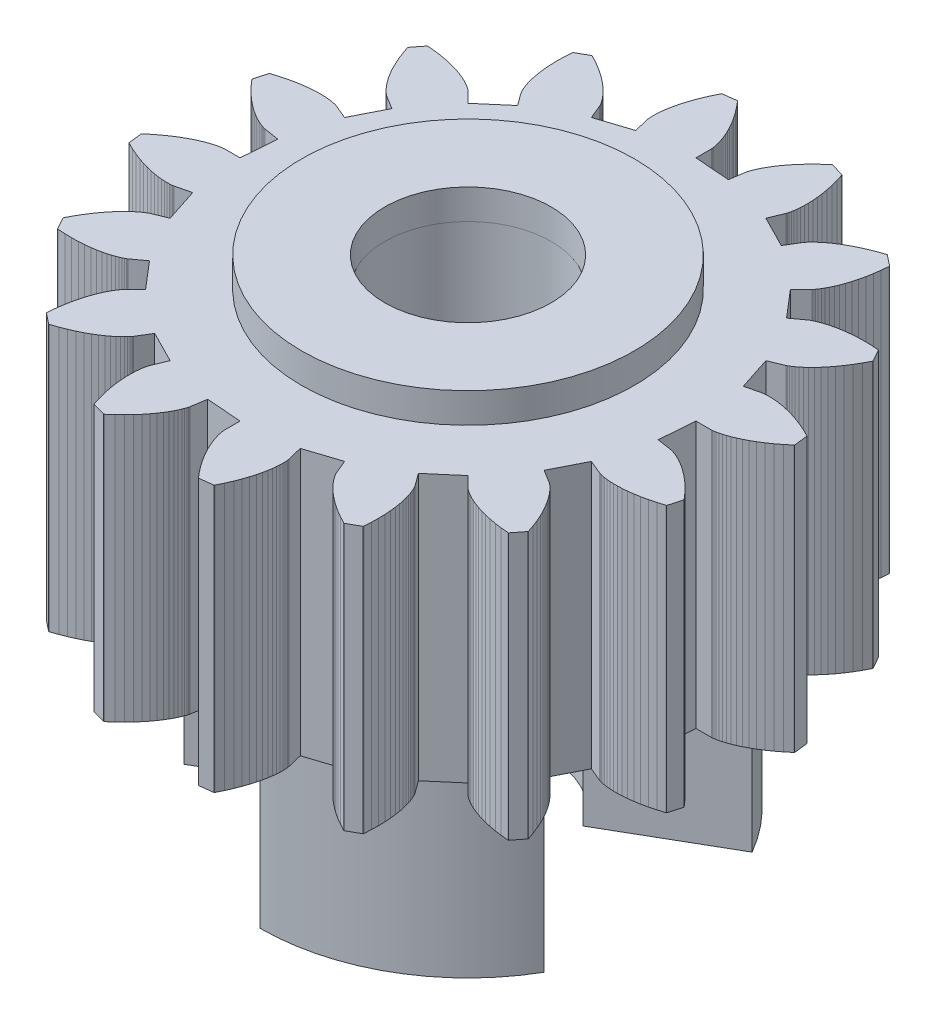
SolidWorks part; units mm, degrees
ref_plane "Front Plane" through (0, 0, 0) normal (0, 0, 1) x (1, 0, 0)
ref_plane "Top Plane" through (0, 0, 0) normal (0, 1, 0) x (1, 0, 0)
ref_plane "Right Plane" through (0, 0, 0) normal (1, 0, 0) x (0, 0, -1)
sketch "Sketch1" plane through (0, 0, 0) normal (0, 1, 0) x (1, 0, 0)
  line L0 (6.85, 0) -> (7.3095, 0)
  line L1 (7.3095, 0) -> (7.322, 0.0006)
  line L2 (7.322, 0.0006) -> (7.3483, 0.0028)
  line L3 (7.3483, 0.0028) -> (7.3883, 0.0079)
  line L4 (7.3883, 0.0079) -> (7.4418, 0.0172)
  line L5 (7.4418, 0.0172) -> (7.5084, 0.0317)
  line L6 (7.5084, 0.0317) -> (7.5878, 0.0526)
  line L7 (7.5878, 0.0526) -> (7.6795, 0.0812)
  line L8 (7.6795, 0.0812) -> (7.7829, 0.1183)
  line L9 (7.7829, 0.1183) -> (7.8975, 0.1653)
  line L10 (7.8975, 0.1653) -> (8.0225, 0.223)
  line L11 (8.0225, 0.223) -> (8.1573, 0.2925)
  line L12 (8.1573, 0.2925) -> (8.3011, 0.3747)
  line L13 (8.3011, 0.3747) -> (8.4528, 0.4705)
  line L14 (8.4528, 0.4705) -> (8.6117, 0.5808)
  line L15 (8.6117, 0.5808) -> (8.7767, 0.7063)
  line L16 (8.7767, 0.7063) -> (8.9467, 0.8478)
  line L17 (8.9467, 0.8478) -> (8.9575, 0.8572)
  line L18 (8.9575, 0.8572) -> (8.9588, 0.8583)
  line L19 (8.9588, 0.8583) -> (8.9589, 0.8586)
  line L20 (8.9589, 0.8586) -> (8.9086, 1.2795)
  line L21 (8.9086, 1.2795) -> (8.9084, 1.2798)
  line L22 (8.9084, 1.2798) -> (8.9068, 1.2806)
  line L23 (8.9068, 1.2806) -> (8.8941, 1.2872)
  line L24 (8.8941, 1.2872) -> (8.6955, 1.3845)
  line L25 (8.6955, 1.3845) -> (8.5056, 1.4676)
  line L26 (8.5056, 1.4676) -> (8.3252, 1.5373)
  line L27 (8.3252, 1.5373) -> (8.1551, 1.5946)
  line L28 (8.1551, 1.5946) -> (7.996, 1.6405)
  line L29 (7.996, 1.6405) -> (7.8486, 1.6762)
  line L30 (7.8486, 1.6762) -> (7.7135, 1.7028)
  line L31 (7.7135, 1.7028) -> (7.5911, 1.7214)
  line L32 (7.5911, 1.7214) -> (7.4818, 1.7331)
  line L33 (7.4818, 1.7331) -> (7.386, 1.7392)
  line L34 (7.386, 1.7392) -> (7.3039, 1.7408)
  line L35 (7.3039, 1.7408) -> (7.2357, 1.7392)
  line L36 (7.2357, 1.7392) -> (7.1816, 1.7356)
  line L37 (7.1816, 1.7356) -> (7.1415, 1.7311)
  line L38 (7.1415, 1.7311) -> (7.1154, 1.7271)
  line L39 (7.1154, 1.7271) -> (7.1031, 1.7247)
  line L40 (7.1031, 1.7247) -> (6.6566, 1.6163)
  line L41 (6.6566, 1.6163) -> (6.3286, 2.6214)
  line L42 (6.3286, 2.6214) -> (6.7531, 2.7972)
  line L43 (6.7531, 2.7972) -> (6.7644, 2.8025)
  line L44 (6.7644, 2.8025) -> (6.7879, 2.8147)
  line L45 (6.7879, 2.8147) -> (6.8229, 2.8347)
  line L46 (6.8229, 2.8347) -> (6.8688, 2.8637)
  line L47 (6.8688, 2.8637) -> (6.9248, 2.9026)
  line L48 (6.9248, 2.9026) -> (6.9901, 2.9524)
  line L49 (6.9901, 2.9524) -> (7.0638, 3.0138)
  line L50 (7.0638, 3.0138) -> (7.1452, 3.0877)
  line L51 (7.1452, 3.0877) -> (7.2331, 3.1749)
  line L52 (7.2331, 3.1749) -> (7.3265, 3.2761)
  line L53 (7.3265, 3.2761) -> (7.4245, 3.3919)
  line L54 (7.4245, 3.3919) -> (7.5258, 3.5228)
  line L55 (7.5258, 3.5228) -> (7.6293, 3.6694)
  line L56 (7.6293, 3.6694) -> (7.7339, 3.8321)
  line L57 (7.7339, 3.8321) -> (7.8383, 4.0112)
  line L58 (7.8383, 4.0112) -> (7.9413, 4.207)
  line L59 (7.9413, 4.207) -> (7.9476, 4.2198)
  line L60 (7.9476, 4.2198) -> (7.9484, 4.2214)
  line L61 (7.9484, 4.2214) -> (7.9484, 4.2217)
  line L62 (7.9484, 4.2217) -> (7.7408, 4.5913)
  line L63 (7.7408, 4.5913) -> (7.7406, 4.5914)
  line L64 (7.7406, 4.5914) -> (7.7388, 4.5916)
  line L65 (7.7388, 4.5916) -> (7.7245, 4.5928)
  line L66 (7.7245, 4.5928) -> (7.5038, 4.6068)
  line L67 (7.5038, 4.6068) -> (7.2965, 4.6108)
  line L68 (7.2965, 4.6108) -> (7.1032, 4.6062)
  line L69 (7.1032, 4.6062) -> (6.9241, 4.594)
  line L70 (6.9241, 4.594) -> (6.7596, 4.5756)
  line L71 (6.7596, 4.5756) -> (6.6097, 4.5522)
  line L72 (6.6097, 4.5522) -> (6.4747, 4.525)
  line L73 (6.4747, 4.525) -> (6.3545, 4.4953)
  line L74 (6.3545, 4.4953) -> (6.249, 4.4644)
  line L75 (6.249, 4.4644) -> (6.1582, 4.4333)
  line L76 (6.1582, 4.4333) -> (6.0817, 4.4034)
  line L77 (6.0817, 4.4034) -> (6.0194, 4.3758)
  line L78 (6.0194, 4.3758) -> (5.9708, 4.3518)
  line L79 (5.9708, 4.3518) -> (5.9354, 4.3323)
  line L80 (5.9354, 4.3323) -> (5.9128, 4.3186)
  line L81 (5.9128, 4.3186) -> (5.9024, 4.3116)
  line L82 (5.9024, 4.3116) -> (5.5314, 4.0406)
  line L83 (5.5314, 4.0406) -> (4.8437, 4.8437)
  line L84 (4.8437, 4.8437) -> (5.1686, 5.1686)
  line L85 (5.1686, 5.1686) -> (5.177, 5.1778)
  line L86 (5.177, 5.1778) -> (5.1941, 5.198)
  line L87 (5.1941, 5.198) -> (5.2187, 5.23)
  line L88 (5.2187, 5.23) -> (5.25, 5.2743)
  line L89 (5.25, 5.2743) -> (5.2869, 5.3317)
  line L90 (5.2869, 5.3317) -> (5.3282, 5.4026)
  line L91 (5.3282, 5.4026) -> (5.3728, 5.4876)
  line L92 (5.3728, 5.4876) -> (5.4197, 5.587)
  line L93 (5.4197, 5.587) -> (5.4675, 5.7012)
  line L94 (5.4675, 5.7012) -> (5.5151, 5.8305)
  line L95 (5.5151, 5.8305) -> (5.5613, 5.9749)
  line L96 (5.5613, 5.9749) -> (5.6048, 6.1347)
  line L97 (5.6048, 6.1347) -> (5.6444, 6.3097)
  line L98 (5.6444, 6.3097) -> (5.6787, 6.5)
  line L99 (5.6787, 6.5) -> (5.7066, 6.7055)
  line L100 (5.7066, 6.7055) -> (5.7268, 6.9258)
  line L101 (5.7268, 6.9258) -> (5.7278, 6.94)
  line L102 (5.7278, 6.94) -> (5.7279, 6.9418)
  line L103 (5.7279, 6.9418) -> (5.7278, 6.9421)
  line L104 (5.7278, 6.9421) -> (5.3946, 7.2041)
  line L105 (5.3946, 7.2041) -> (5.3943, 7.2041)
  line L106 (5.3943, 7.2041) -> (5.3926, 7.2036)
  line L107 (5.3926, 7.2036) -> (5.3789, 7.1993)
  line L108 (5.3789, 7.1993) -> (5.1696, 7.1277)
  line L109 (5.1696, 7.1277) -> (4.9766, 7.0521)
  line L110 (4.9766, 7.0521) -> (4.7998, 6.9738)
  line L111 (4.7998, 6.9738) -> (4.639, 6.894)
  line L112 (4.639, 6.894) -> (4.494, 6.8141)
  line L113 (4.494, 6.8141) -> (4.3645, 6.7351)
  line L114 (4.3645, 6.7351) -> (4.2502, 6.6583)
  line L115 (4.2502, 6.6583) -> (4.1505, 6.5849)
  line L116 (4.1505, 6.5849) -> (4.0649, 6.5159)
  line L117 (4.0649, 6.5159) -> (3.9929, 6.4525)
  line L118 (3.9929, 6.4525) -> (3.9337, 6.3956)
  line L119 (3.9337, 6.3956) -> (3.8866, 6.3463)
  line L120 (3.8866, 6.3463) -> (3.8509, 6.3054)
  line L121 (3.8509, 6.3054) -> (3.8257, 6.2739)
  line L122 (3.8257, 6.2739) -> (3.8101, 6.2526)
  line L123 (3.8101, 6.2526) -> (3.8031, 6.2422)
  line L124 (3.8031, 6.2422) -> (3.564, 5.8498)
  line L125 (3.564, 5.8498) -> (2.6214, 6.3286)
  line L126 (2.6214, 6.3286) -> (2.7972, 6.7531)
  line L127 (2.7972, 6.7531) -> (2.8015, 6.7648)
  line L128 (2.8015, 6.7648) -> (2.8095, 6.79)
  line L129 (2.8095, 6.79) -> (2.8201, 6.829)
  line L130 (2.8201, 6.829) -> (2.832, 6.8819)
  line L131 (2.832, 6.8819) -> (2.8441, 6.949)
  line L132 (2.8441, 6.949) -> (2.8551, 7.0304)
  line L133 (2.8551, 7.0304) -> (2.8638, 7.126)
  line L134 (2.8638, 7.126) -> (2.869, 7.2357)
  line L135 (2.869, 7.2357) -> (2.8695, 7.3596)
  line L136 (2.8695, 7.3596) -> (2.8641, 7.4972)
  line L137 (2.8641, 7.4972) -> (2.8515, 7.6483)
  line L138 (2.8515, 7.6483) -> (2.8305, 7.8126)
  line L139 (2.8305, 7.8126) -> (2.8001, 7.9894)
  line L140 (2.8001, 7.9894) -> (2.759, 8.1784)
  line L141 (2.759, 8.1784) -> (2.7062, 8.3789)
  line L142 (2.7062, 8.3789) -> (2.6405, 8.5901)
  line L143 (2.6405, 8.5901) -> (2.636, 8.6037)
  line L144 (2.636, 8.6037) -> (2.6354, 8.6054)
  line L145 (2.6354, 8.6054) -> (2.6352, 8.6056)
  line L146 (2.6352, 8.6056) -> (2.227, 8.7201)
  line L147 (2.227, 8.7201) -> (2.2268, 8.72)
  line L148 (2.2268, 8.72) -> (2.2254, 8.7189)
  line L149 (2.2254, 8.7189) -> (2.2144, 8.7097)
  line L150 (2.2144, 8.7097) -> (2.0485, 8.5634)
  line L151 (2.0485, 8.5634) -> (1.8991, 8.4197)
  line L152 (1.8991, 8.4197) -> (1.7657, 8.2797)
  line L153 (1.7657, 8.2797) -> (1.6476, 8.1445)
  line L154 (1.6476, 8.1445) -> (1.5443, 8.0152)
  line L155 (1.5443, 8.0152) -> (1.4549, 7.8927)
  line L156 (1.4549, 7.8927) -> (1.3786, 7.778)
  line L157 (1.3786, 7.778) -> (1.3146, 7.672)
  line L158 (1.3146, 7.672) -> (1.262, 7.5755)
  line L159 (1.262, 7.5755) -> (1.2197, 7.4893)
  line L160 (1.2197, 7.4893) -> (1.1868, 7.4141)
  line L161 (1.1868, 7.4141) -> (1.1622, 7.3505)
  line L162 (1.1622, 7.3505) -> (1.1448, 7.2991)
  line L163 (1.1448, 7.2991) -> (1.1336, 7.2604)
  line L164 (1.1336, 7.2604) -> (1.1273, 7.2347)
  line L165 (1.1273, 7.2347) -> (1.1248, 7.2224)
  line L166 (1.1248, 7.2224) -> (1.0541, 6.7684)
  line L167 (1.0541, 6.7684) -> (0, 6.85)
  line L168 (0, 6.85) -> (0, 7.3095)
  line L169 (0, 7.3095) -> (-0.0006, 7.322)
  line L170 (-0.0006, 7.322) -> (-0.0028, 7.3483)
  line L171 (-0.0028, 7.3483) -> (-0.0079, 7.3883)
  line L172 (-0.0079, 7.3883) -> (-0.0172, 7.4418)
  line L173 (-0.0172, 7.4418) -> (-0.0317, 7.5084)
  line L174 (-0.0317, 7.5084) -> (-0.0526, 7.5878)
  line L175 (-0.0526, 7.5878) -> (-0.0812, 7.6795)
  line L176 (-0.0812, 7.6795) -> (-0.1183, 7.7829)
  line L177 (-0.1183, 7.7829) -> (-0.1653, 7.8975)
  line L178 (-0.1653, 7.8975) -> (-0.223, 8.0225)
  line L179 (-0.223, 8.0225) -> (-0.2925, 8.1573)
  line L180 (-0.2925, 8.1573) -> (-0.3747, 8.3011)
  line L181 (-0.3747, 8.3011) -> (-0.4705, 8.4528)
  line L182 (-0.4705, 8.4528) -> (-0.5808, 8.6117)
  line L183 (-0.5808, 8.6117) -> (-0.7063, 8.7767)
  line L184 (-0.7063, 8.7767) -> (-0.8478, 8.9467)
  line L185 (-0.8478, 8.9467) -> (-0.8572, 8.9575)
  line L186 (-0.8572, 8.9575) -> (-0.8583, 8.9588)
  line L187 (-0.8583, 8.9588) -> (-0.8586, 8.9589)
  line L188 (-0.8586, 8.9589) -> (-1.2795, 8.9086)
  line L189 (-1.2795, 8.9086) -> (-1.2798, 8.9084)
  line L190 (-1.2798, 8.9084) -> (-1.2806, 8.9068)
  line L191 (-1.2806, 8.9068) -> (-1.2872, 8.8941)
  line L192 (-1.2872, 8.8941) -> (-1.3845, 8.6955)
  line L193 (-1.3845, 8.6955) -> (-1.4676, 8.5056)
  line L194 (-1.4676, 8.5056) -> (-1.5373, 8.3252)
  line L195 (-1.5373, 8.3252) -> (-1.5946, 8.1551)
  line L196 (-1.5946, 8.1551) -> (-1.6405, 7.996)
  line L197 (-1.6405, 7.996) -> (-1.6762, 7.8486)
  line L198 (-1.6762, 7.8486) -> (-1.7028, 7.7135)
  line L199 (-1.7028, 7.7135) -> (-1.7214, 7.5911)
  line L200 (-1.7214, 7.5911) -> (-1.7331, 7.4818)
  line L201 (-1.7331, 7.4818) -> (-1.7392, 7.386)
  line L202 (-1.7392, 7.386) -> (-1.7408, 7.3039)
  line L203 (-1.7408, 7.3039) -> (-1.7392, 7.2357)
  line L204 (-1.7392, 7.2357) -> (-1.7356, 7.1816)
  line L205 (-1.7356, 7.1816) -> (-1.7311, 7.1415)
  line L206 (-1.7311, 7.1415) -> (-1.7271, 7.1154)
  line L207 (-1.7271, 7.1154) -> (-1.7247, 7.1031)
  line L208 (-1.7247, 7.1031) -> (-1.6163, 6.6566)
  line L209 (-1.6163, 6.6566) -> (-2.6214, 6.3286)
  line L210 (-2.6214, 6.3286) -> (-2.7972, 6.7531)
  line L211 (-2.7972, 6.7531) -> (-2.8025, 6.7644)
  line L212 (-2.8025, 6.7644) -> (-2.8147, 6.7879)
  line L213 (-2.8147, 6.7879) -> (-2.8347, 6.8229)
  line L214 (-2.8347, 6.8229) -> (-2.8637, 6.8688)
  line L215 (-2.8637, 6.8688) -> (-2.9026, 6.9248)
  line L216 (-2.9026, 6.9248) -> (-2.9524, 6.9901)
  line L217 (-2.9524, 6.9901) -> (-3.0138, 7.0638)
  line L218 (-3.0138, 7.0638) -> (-3.0877, 7.1452)
  line L219 (-3.0877, 7.1452) -> (-3.1749, 7.2331)
  line L220 (-3.1749, 7.2331) -> (-3.2761, 7.3265)
  line L221 (-3.2761, 7.3265) -> (-3.3919, 7.4245)
  line L222 (-3.3919, 7.4245) -> (-3.5228, 7.5258)
  line L223 (-3.5228, 7.5258) -> (-3.6694, 7.6293)
  line L224 (-3.6694, 7.6293) -> (-3.8321, 7.7339)
  line L225 (-3.8321, 7.7339) -> (-4.0112, 7.8383)
  line L226 (-4.0112, 7.8383) -> (-4.207, 7.9413)
  line L227 (-4.207, 7.9413) -> (-4.2198, 7.9476)
  line L228 (-4.2198, 7.9476) -> (-4.2214, 7.9484)
  line L229 (-4.2214, 7.9484) -> (-4.2217, 7.9484)
  line L230 (-4.2217, 7.9484) -> (-4.5913, 7.7408)
  line L231 (-4.5913, 7.7408) -> (-4.5914, 7.7406)
  line L232 (-4.5914, 7.7406) -> (-4.5916, 7.7388)
  line L233 (-4.5916, 7.7388) -> (-4.5928, 7.7245)
  line L234 (-4.5928, 7.7245) -> (-4.6068, 7.5038)
  line L235 (-4.6068, 7.5038) -> (-4.6108, 7.2965)
  line L236 (-4.6108, 7.2965) -> (-4.6062, 7.1032)
  line L237 (-4.6062, 7.1032) -> (-4.594, 6.9241)
  line L238 (-4.594, 6.9241) -> (-4.5756, 6.7596)
  line L239 (-4.5756, 6.7596) -> (-4.5522, 6.6097)
  line L240 (-4.5522, 6.6097) -> (-4.525, 6.4747)
  line L241 (-4.525, 6.4747) -> (-4.4953, 6.3545)
  line L242 (-4.4953, 6.3545) -> (-4.4644, 6.249)
  line L243 (-4.4644, 6.249) -> (-4.4333, 6.1582)
  line L244 (-4.4333, 6.1582) -> (-4.4034, 6.0817)
  line L245 (-4.4034, 6.0817) -> (-4.3758, 6.0194)
  line L246 (-4.3758, 6.0194) -> (-4.3518, 5.9708)
  line L247 (-4.3518, 5.9708) -> (-4.3323, 5.9354)
  line L248 (-4.3323, 5.9354) -> (-4.3186, 5.9128)
  line L249 (-4.3186, 5.9128) -> (-4.3116, 5.9024)
  line L250 (-4.3116, 5.9024) -> (-4.0406, 5.5314)
  line L251 (-4.0406, 5.5314) -> (-4.8437, 4.8437)
  line L252 (-4.8437, 4.8437) -> (-5.1686, 5.1686)
  line L253 (-5.1686, 5.1686) -> (-5.1778, 5.177)
  line L254 (-5.1778, 5.177) -> (-5.198, 5.1941)
  line L255 (-5.198, 5.1941) -> (-5.23, 5.2187)
  line L256 (-5.23, 5.2187) -> (-5.2743, 5.25)
  line L257 (-5.2743, 5.25) -> (-5.3317, 5.2869)
  line L258 (-5.3317, 5.2869) -> (-5.4026, 5.3282)
  line L259 (-5.4026, 5.3282) -> (-5.4876, 5.3728)
  line L260 (-5.4876, 5.3728) -> (-5.587, 5.4197)
  line L261 (-5.587, 5.4197) -> (-5.7012, 5.4675)
  line L262 (-5.7012, 5.4675) -> (-5.8305, 5.5151)
  line L263 (-5.8305, 5.5151) -> (-5.9749, 5.5613)
  line L264 (-5.9749, 5.5613) -> (-6.1347, 5.6048)
  line L265 (-6.1347, 5.6048) -> (-6.3097, 5.6444)
  line L266 (-6.3097, 5.6444) -> (-6.5, 5.6787)
  line L267 (-6.5, 5.6787) -> (-6.7055, 5.7066)
  line L268 (-6.7055, 5.7066) -> (-6.9258, 5.7268)
  line L269 (-6.9258, 5.7268) -> (-6.94, 5.7278)
  line L270 (-6.94, 5.7278) -> (-6.9418, 5.7279)
  line L271 (-6.9418, 5.7279) -> (-6.9421, 5.7278)
  line L272 (-6.9421, 5.7278) -> (-7.2041, 5.3946)
  line L273 (-7.2041, 5.3946) -> (-7.2041, 5.3943)
  line L274 (-7.2041, 5.3943) -> (-7.2036, 5.3926)
  line L275 (-7.2036, 5.3926) -> (-7.1993, 5.3789)
  line L276 (-7.1993, 5.3789) -> (-7.1277, 5.1696)
  line L277 (-7.1277, 5.1696) -> (-7.0521, 4.9766)
  line L278 (-7.0521, 4.9766) -> (-6.9738, 4.7998)
  line L279 (-6.9738, 4.7998) -> (-6.894, 4.639)
  line L280 (-6.894, 4.639) -> (-6.8141, 4.494)
  line L281 (-6.8141, 4.494) -> (-6.7351, 4.3645)
  line L282 (-6.7351, 4.3645) -> (-6.6583, 4.2502)
  line L283 (-6.6583, 4.2502) -> (-6.5849, 4.1505)
  line L284 (-6.5849, 4.1505) -> (-6.5159, 4.0649)
  line L285 (-6.5159, 4.0649) -> (-6.4525, 3.9929)
  line L286 (-6.4525, 3.9929) -> (-6.3956, 3.9337)
  line L287 (-6.3956, 3.9337) -> (-6.3463, 3.8866)
  line L288 (-6.3463, 3.8866) -> (-6.3054, 3.8509)
  line L289 (-6.3054, 3.8509) -> (-6.2739, 3.8257)
  line L290 (-6.2739, 3.8257) -> (-6.2526, 3.8101)
  line L291 (-6.2526, 3.8101) -> (-6.2422, 3.8031)
  line L292 (-6.2422, 3.8031) -> (-5.8498, 3.564)
  line L293 (-5.8498, 3.564) -> (-6.3286, 2.6214)
  line L294 (-6.3286, 2.6214) -> (-6.7531, 2.7972)
  line L295 (-6.7531, 2.7972) -> (-6.7648, 2.8015)
  line L296 (-6.7648, 2.8015) -> (-6.79, 2.8095)
  line L297 (-6.79, 2.8095) -> (-6.829, 2.8201)
  line L298 (-6.829, 2.8201) -> (-6.8819, 2.832)
  line L299 (-6.8819, 2.832) -> (-6.949, 2.8441)
  line L300 (-6.949, 2.8441) -> (-7.0304, 2.8551)
  line L301 (-7.0304, 2.8551) -> (-7.126, 2.8638)
  line L302 (-7.126, 2.8638) -> (-7.2357, 2.869)
  line L303 (-7.2357, 2.869) -> (-7.3596, 2.8695)
  line L304 (-7.3596, 2.8695) -> (-7.4972, 2.8641)
  line L305 (-7.4972, 2.8641) -> (-7.6483, 2.8515)
  line L306 (-7.6483, 2.8515) -> (-7.8126, 2.8305)
  line L307 (-7.8126, 2.8305) -> (-7.9894, 2.8001)
  line L308 (-7.9894, 2.8001) -> (-8.1784, 2.759)
  line L309 (-8.1784, 2.759) -> (-8.3789, 2.7062)
  line L310 (-8.3789, 2.7062) -> (-8.5901, 2.6405)
  line L311 (-8.5901, 2.6405) -> (-8.6037, 2.636)
  line L312 (-8.6037, 2.636) -> (-8.6054, 2.6354)
  line L313 (-8.6054, 2.6354) -> (-8.6056, 2.6352)
  line L314 (-8.6056, 2.6352) -> (-8.7201, 2.227)
  line L315 (-8.7201, 2.227) -> (-8.72, 2.2268)
  line L316 (-8.72, 2.2268) -> (-8.7189, 2.2254)
  line L317 (-8.7189, 2.2254) -> (-8.7097, 2.2144)
  line L318 (-8.7097, 2.2144) -> (-8.5634, 2.0485)
  line L319 (-8.5634, 2.0485) -> (-8.4197, 1.8991)
  line L320 (-8.4197, 1.8991) -> (-8.2797, 1.7657)
  line L321 (-8.2797, 1.7657) -> (-8.1445, 1.6476)
  line L322 (-8.1445, 1.6476) -> (-8.0152, 1.5443)
  line L323 (-8.0152, 1.5443) -> (-7.8927, 1.4549)
  line L324 (-7.8927, 1.4549) -> (-7.778, 1.3786)
  line L325 (-7.778, 1.3786) -> (-7.672, 1.3146)
  line L326 (-7.672, 1.3146) -> (-7.5755, 1.262)
  line L327 (-7.5755, 1.262) -> (-7.4893, 1.2197)
  line L328 (-7.4893, 1.2197) -> (-7.4141, 1.1868)
  line L329 (-7.4141, 1.1868) -> (-7.3505, 1.1622)
  line L330 (-7.3505, 1.1622) -> (-7.2991, 1.1448)
  line L331 (-7.2991, 1.1448) -> (-7.2604, 1.1336)
  line L332 (-7.2604, 1.1336) -> (-7.2347, 1.1273)
  line L333 (-7.2347, 1.1273) -> (-7.2224, 1.1248)
  line L334 (-7.2224, 1.1248) -> (-6.7684, 1.0541)
  line L335 (-6.7684, 1.0541) -> (-6.85, 0)
  line L336 (-6.85, 0) -> (-7.3095, 0)
  line L337 (-7.3095, 0) -> (-7.322, -0.0006)
  line L338 (-7.322, -0.0006) -> (-7.3483, -0.0028)
  line L339 (-7.3483, -0.0028) -> (-7.3883, -0.0079)
  line L340 (-7.3883, -0.0079) -> (-7.4418, -0.0172)
  line L341 (-7.4418, -0.0172) -> (-7.5084, -0.0317)
  line L342 (-7.5084, -0.0317) -> (-7.5878, -0.0526)
  line L343 (-7.5878, -0.0526) -> (-7.6795, -0.0812)
  line L344 (-7.6795, -0.0812) -> (-7.7829, -0.1183)
  line L345 (-7.7829, -0.1183) -> (-7.8975, -0.1653)
  line L346 (-7.8975, -0.1653) -> (-8.0225, -0.223)
  line L347 (-8.0225, -0.223) -> (-8.1573, -0.2925)
  line L348 (-8.1573, -0.2925) -> (-8.3011, -0.3747)
  line L349 (-8.3011, -0.3747) -> (-8.4528, -0.4705)
  line L350 (-8.4528, -0.4705) -> (-8.6117, -0.5808)
  line L351 (-8.6117, -0.5808) -> (-8.7767, -0.7063)
  line L352 (-8.7767, -0.7063) -> (-8.9467, -0.8478)
  line L353 (-8.9467, -0.8478) -> (-8.9575, -0.8572)
  line L354 (-8.9575, -0.8572) -> (-8.9588, -0.8583)
  line L355 (-8.9588, -0.8583) -> (-8.9589, -0.8586)
  line L356 (-8.9589, -0.8586) -> (-8.9086, -1.2795)
  line L357 (-8.9086, -1.2795) -> (-8.9084, -1.2798)
  line L358 (-8.9084, -1.2798) -> (-8.9068, -1.2806)
  line L359 (-8.9068, -1.2806) -> (-8.8941, -1.2872)
  line L360 (-8.8941, -1.2872) -> (-8.6955, -1.3845)
  line L361 (-8.6955, -1.3845) -> (-8.5056, -1.4676)
  line L362 (-8.5056, -1.4676) -> (-8.3252, -1.5373)
  line L363 (-8.3252, -1.5373) -> (-8.1551, -1.5946)
  line L364 (-8.1551, -1.5946) -> (-7.996, -1.6405)
  line L365 (-7.996, -1.6405) -> (-7.8486, -1.6762)
  line L366 (-7.8486, -1.6762) -> (-7.7135, -1.7028)
  line L367 (-7.7135, -1.7028) -> (-7.5911, -1.7214)
  line L368 (-7.5911, -1.7214) -> (-7.4818, -1.7331)
  line L369 (-7.4818, -1.7331) -> (-7.386, -1.7392)
  line L370 (-7.386, -1.7392) -> (-7.3039, -1.7408)
  line L371 (-7.3039, -1.7408) -> (-7.2357, -1.7392)
  line L372 (-7.2357, -1.7392) -> (-7.1816, -1.7356)
  line L373 (-7.1816, -1.7356) -> (-7.1415, -1.7311)
  line L374 (-7.1415, -1.7311) -> (-7.1154, -1.7271)
  line L375 (-7.1154, -1.7271) -> (-7.1031, -1.7247)
  line L376 (-7.1031, -1.7247) -> (-6.6566, -1.6163)
  line L377 (-6.6566, -1.6163) -> (-6.3286, -2.6214)
  line L378 (-6.3286, -2.6214) -> (-6.7531, -2.7972)
  line L379 (-6.7531, -2.7972) -> (-6.7644, -2.8025)
  line L380 (-6.7644, -2.8025) -> (-6.7879, -2.8147)
  line L381 (-6.7879, -2.8147) -> (-6.8229, -2.8347)
  line L382 (-6.8229, -2.8347) -> (-6.8688, -2.8637)
  line L383 (-6.8688, -2.8637) -> (-6.9248, -2.9026)
  line L384 (-6.9248, -2.9026) -> (-6.9901, -2.9524)
  line L385 (-6.9901, -2.9524) -> (-7.0638, -3.0138)
  line L386 (-7.0638, -3.0138) -> (-7.1452, -3.0877)
  line L387 (-7.1452, -3.0877) -> (-7.2331, -3.1749)
  line L388 (-7.2331, -3.1749) -> (-7.3265, -3.2761)
  line L389 (-7.3265, -3.2761) -> (-7.4245, -3.3919)
  line L390 (-7.4245, -3.3919) -> (-7.5258, -3.5228)
  line L391 (-7.5258, -3.5228) -> (-7.6293, -3.6694)
  line L392 (-7.6293, -3.6694) -> (-7.7339, -3.8321)
  line L393 (-7.7339, -3.8321) -> (-7.8383, -4.0112)
  line L394 (-7.8383, -4.0112) -> (-7.9413, -4.207)
  line L395 (-7.9413, -4.207) -> (-7.9476, -4.2198)
  line L396 (-7.9476, -4.2198) -> (-7.9484, -4.2214)
  line L397 (-7.9484, -4.2214) -> (-7.9484, -4.2217)
  line L398 (-7.9484, -4.2217) -> (-7.7408, -4.5913)
  line L399 (-7.7408, -4.5913) -> (-7.7406, -4.5914)
  line L400 (-7.7406, -4.5914) -> (-7.7388, -4.5916)
  line L401 (-7.7388, -4.5916) -> (-7.7245, -4.5928)
  line L402 (-7.7245, -4.5928) -> (-7.5038, -4.6068)
  line L403 (-7.5038, -4.6068) -> (-7.2965, -4.6108)
  line L404 (-7.2965, -4.6108) -> (-7.1032, -4.6062)
  line L405 (-7.1032, -4.6062) -> (-6.9241, -4.594)
  line L406 (-6.9241, -4.594) -> (-6.7596, -4.5756)
  line L407 (-6.7596, -4.5756) -> (-6.6097, -4.5522)
  line L408 (-6.6097, -4.5522) -> (-6.4747, -4.525)
  line L409 (-6.4747, -4.525) -> (-6.3545, -4.4953)
  line L410 (-6.3545, -4.4953) -> (-6.249, -4.4644)
  line L411 (-6.249, -4.4644) -> (-6.1582, -4.4333)
  line L412 (-6.1582, -4.4333) -> (-6.0817, -4.4034)
  line L413 (-6.0817, -4.4034) -> (-6.0194, -4.3758)
  line L414 (-6.0194, -4.3758) -> (-5.9708, -4.3518)
  line L415 (-5.9708, -4.3518) -> (-5.9354, -4.3323)
  line L416 (-5.9354, -4.3323) -> (-5.9128, -4.3186)
  line L417 (-5.9128, -4.3186) -> (-5.9024, -4.3116)
  line L418 (-5.9024, -4.3116) -> (-5.5314, -4.0406)
  line L419 (-5.5314, -4.0406) -> (-4.8437, -4.8437)
  line L420 (-4.8437, -4.8437) -> (-5.1686, -5.1686)
  line L421 (-5.1686, -5.1686) -> (-5.177, -5.1778)
  line L422 (-5.177, -5.1778) -> (-5.1941, -5.198)
  line L423 (-5.1941, -5.198) -> (-5.2187, -5.23)
  line L424 (-5.2187, -5.23) -> (-5.25, -5.2743)
  line L425 (-5.25, -5.2743) -> (-5.2869, -5.3317)
  line L426 (-5.2869, -5.3317) -> (-5.3282, -5.4026)
  line L427 (-5.3282, -5.4026) -> (-5.3728, -5.4876)
  line L428 (-5.3728, -5.4876) -> (-5.4197, -5.587)
  line L429 (-5.4197, -5.587) -> (-5.4675, -5.7012)
  line L430 (-5.4675, -5.7012) -> (-5.5151, -5.8305)
  line L431 (-5.5151, -5.8305) -> (-5.5613, -5.9749)
  line L432 (-5.5613, -5.9749) -> (-5.6048, -6.1347)
  line L433 (-5.6048, -6.1347) -> (-5.6444, -6.3097)
  line L434 (-5.6444, -6.3097) -> (-5.6787, -6.5)
  line L435 (-5.6787, -6.5) -> (-5.7066, -6.7055)
  line L436 (-5.7066, -6.7055) -> (-5.7268, -6.9258)
  line L437 (-5.7268, -6.9258) -> (-5.7278, -6.94)
  line L438 (-5.7278, -6.94) -> (-5.7279, -6.9418)
  line L439 (-5.7279, -6.9418) -> (-5.7278, -6.9421)
  line L440 (-5.7278, -6.9421) -> (-5.3946, -7.2041)
  line L441 (-5.3946, -7.2041) -> (-5.3943, -7.2041)
  line L442 (-5.3943, -7.2041) -> (-5.3926, -7.2036)
  line L443 (-5.3926, -7.2036) -> (-5.3789, -7.1993)
  line L444 (-5.3789, -7.1993) -> (-5.1696, -7.1277)
  line L445 (-5.1696, -7.1277) -> (-4.9766, -7.0521)
  line L446 (-4.9766, -7.0521) -> (-4.7998, -6.9738)
  line L447 (-4.7998, -6.9738) -> (-4.639, -6.894)
  line L448 (-4.639, -6.894) -> (-4.494, -6.8141)
  line L449 (-4.494, -6.8141) -> (-4.3645, -6.7351)
  line L450 (-4.3645, -6.7351) -> (-4.2502, -6.6583)
  line L451 (-4.2502, -6.6583) -> (-4.1505, -6.5849)
  line L452 (-4.1505, -6.5849) -> (-4.0649, -6.5159)
  line L453 (-4.0649, -6.5159) -> (-3.9929, -6.4525)
  line L454 (-3.9929, -6.4525) -> (-3.9337, -6.3956)
  line L455 (-3.9337, -6.3956) -> (-3.8866, -6.3463)
  line L456 (-3.8866, -6.3463) -> (-3.8509, -6.3054)
  line L457 (-3.8509, -6.3054) -> (-3.8257, -6.2739)
  line L458 (-3.8257, -6.2739) -> (-3.8101, -6.2526)
  line L459 (-3.8101, -6.2526) -> (-3.8031, -6.2422)
  line L460 (-3.8031, -6.2422) -> (-3.564, -5.8498)
  line L461 (-3.564, -5.8498) -> (-2.6214, -6.3286)
  line L462 (-2.6214, -6.3286) -> (-2.7972, -6.7531)
  line L463 (-2.7972, -6.7531) -> (-2.8015, -6.7648)
  line L464 (-2.8015, -6.7648) -> (-2.8095, -6.79)
  line L465 (-2.8095, -6.79) -> (-2.8201, -6.829)
  line L466 (-2.8201, -6.829) -> (-2.832, -6.8819)
  line L467 (-2.832, -6.8819) -> (-2.8441, -6.949)
  line L468 (-2.8441, -6.949) -> (-2.8551, -7.0304)
  line L469 (-2.8551, -7.0304) -> (-2.8638, -7.126)
  line L470 (-2.8638, -7.126) -> (-2.869, -7.2357)
  line L471 (-2.869, -7.2357) -> (-2.8695, -7.3596)
  line L472 (-2.8695, -7.3596) -> (-2.8641, -7.4972)
  line L473 (-2.8641, -7.4972) -> (-2.8515, -7.6483)
  line L474 (-2.8515, -7.6483) -> (-2.8305, -7.8126)
  line L475 (-2.8305, -7.8126) -> (-2.8001, -7.9894)
  line L476 (-2.8001, -7.9894) -> (-2.759, -8.1784)
  line L477 (-2.759, -8.1784) -> (-2.7062, -8.3789)
  line L478 (-2.7062, -8.3789) -> (-2.6405, -8.5901)
  line L479 (-2.6405, -8.5901) -> (-2.636, -8.6037)
  line L480 (-2.636, -8.6037) -> (-2.6354, -8.6054)
  line L481 (-2.6354, -8.6054) -> (-2.6352, -8.6056)
  line L482 (-2.6352, -8.6056) -> (-2.227, -8.7201)
  line L483 (-2.227, -8.7201) -> (-2.2268, -8.72)
  line L484 (-2.2268, -8.72) -> (-2.2254, -8.7189)
  line L485 (-2.2254, -8.7189) -> (-2.2144, -8.7097)
  line L486 (-2.2144, -8.7097) -> (-2.0485, -8.5634)
  line L487 (-2.0485, -8.5634) -> (-1.8991, -8.4197)
  line L488 (-1.8991, -8.4197) -> (-1.7657, -8.2797)
  line L489 (-1.7657, -8.2797) -> (-1.6476, -8.1445)
  line L490 (-1.6476, -8.1445) -> (-1.5443, -8.0152)
  line L491 (-1.5443, -8.0152) -> (-1.4549, -7.8927)
  line L492 (-1.4549, -7.8927) -> (-1.3786, -7.778)
  line L493 (-1.3786, -7.778) -> (-1.3146, -7.672)
  line L494 (-1.3146, -7.672) -> (-1.262, -7.5755)
  line L495 (-1.262, -7.5755) -> (-1.2197, -7.4893)
  line L496 (-1.2197, -7.4893) -> (-1.1868, -7.4141)
  line L497 (-1.1868, -7.4141) -> (-1.1622, -7.3505)
  line L498 (-1.1622, -7.3505) -> (-1.1448, -7.2991)
  line L499 (-1.1448, -7.2991) -> (-1.1336, -7.2604)
  line L500 (-1.1336, -7.2604) -> (-1.1273, -7.2347)
  line L501 (-1.1273, -7.2347) -> (-1.1248, -7.2224)
  line L502 (-1.1248, -7.2224) -> (-1.0541, -6.7684)
  line L503 (-1.0541, -6.7684) -> (0, -6.85)
  line L504 (0, -6.85) -> (0, -7.3095)
  line L505 (0, -7.3095) -> (0.0006, -7.322)
  line L506 (0.0006, -7.322) -> (0.0028, -7.3483)
  line L507 (0.0028, -7.3483) -> (0.0079, -7.3883)
  line L508 (0.0079, -7.3883) -> (0.0172, -7.4418)
  line L509 (0.0172, -7.4418) -> (0.0317, -7.5084)
  line L510 (0.0317, -7.5084) -> (0.0526, -7.5878)
  line L511 (0.0526, -7.5878) -> (0.0812, -7.6795)
  line L512 (0.0812, -7.6795) -> (0.1183, -7.7829)
  line L513 (0.1183, -7.7829) -> (0.1653, -7.8975)
  line L514 (0.1653, -7.8975) -> (0.223, -8.0225)
  line L515 (0.223, -8.0225) -> (0.2925, -8.1573)
  line L516 (0.2925, -8.1573) -> (0.3747, -8.3011)
  line L517 (0.3747, -8.3011) -> (0.4705, -8.4528)
  line L518 (0.4705, -8.4528) -> (0.5808, -8.6117)
  line L519 (0.5808, -8.6117) -> (0.7063, -8.7767)
  line L520 (0.7063, -8.7767) -> (0.8478, -8.9467)
  line L521 (0.8478, -8.9467) -> (0.8572, -8.9575)
  line L522 (0.8572, -8.9575) -> (0.8583, -8.9588)
  line L523 (0.8583, -8.9588) -> (0.8586, -8.9589)
  line L524 (0.8586, -8.9589) -> (1.2795, -8.9086)
  line L525 (1.2795, -8.9086) -> (1.2798, -8.9084)
  line L526 (1.2798, -8.9084) -> (1.2806, -8.9068)
  line L527 (1.2806, -8.9068) -> (1.2872, -8.8941)
  line L528 (1.2872, -8.8941) -> (1.3845, -8.6955)
  line L529 (1.3845, -8.6955) -> (1.4676, -8.5056)
  line L530 (1.4676, -8.5056) -> (1.5373, -8.3252)
  line L531 (1.5373, -8.3252) -> (1.5946, -8.1551)
  line L532 (1.5946, -8.1551) -> (1.6405, -7.996)
  line L533 (1.6405, -7.996) -> (1.6762, -7.8486)
  line L534 (1.6762, -7.8486) -> (1.7028, -7.7135)
  line L535 (1.7028, -7.7135) -> (1.7214, -7.5911)
  line L536 (1.7214, -7.5911) -> (1.7331, -7.4818)
  line L537 (1.7331, -7.4818) -> (1.7392, -7.386)
  line L538 (1.7392, -7.386) -> (1.7408, -7.3039)
  line L539 (1.7408, -7.3039) -> (1.7392, -7.2357)
  line L540 (1.7392, -7.2357) -> (1.7356, -7.1816)
  line L541 (1.7356, -7.1816) -> (1.7311, -7.1415)
  line L542 (1.7311, -7.1415) -> (1.7271, -7.1154)
  line L543 (1.7271, -7.1154) -> (1.7247, -7.1031)
  line L544 (1.7247, -7.1031) -> (1.6163, -6.6566)
  line L545 (1.6163, -6.6566) -> (2.6214, -6.3286)
  line L546 (2.6214, -6.3286) -> (2.7972, -6.7531)
  line L547 (2.7972, -6.7531) -> (2.8025, -6.7644)
  line L548 (2.8025, -6.7644) -> (2.8147, -6.7879)
  line L549 (2.8147, -6.7879) -> (2.8347, -6.8229)
  line L550 (2.8347, -6.8229) -> (2.8637, -6.8688)
  line L551 (2.8637, -6.8688) -> (2.9026, -6.9248)
  line L552 (2.9026, -6.9248) -> (2.9524, -6.9901)
  line L553 (2.9524, -6.9901) -> (3.0138, -7.0638)
  line L554 (3.0138, -7.0638) -> (3.0877, -7.1452)
  line L555 (3.0877, -7.1452) -> (3.1749, -7.2331)
  line L556 (3.1749, -7.2331) -> (3.2761, -7.3265)
  line L557 (3.2761, -7.3265) -> (3.3919, -7.4245)
  line L558 (3.3919, -7.4245) -> (3.5228, -7.5258)
  line L559 (3.5228, -7.5258) -> (3.6694, -7.6293)
  line L560 (3.6694, -7.6293) -> (3.8321, -7.7339)
  line L561 (3.8321, -7.7339) -> (4.0112, -7.8383)
  line L562 (4.0112, -7.8383) -> (4.207, -7.9413)
  line L563 (4.207, -7.9413) -> (4.2198, -7.9476)
  line L564 (4.2198, -7.9476) -> (4.2214, -7.9484)
  line L565 (4.2214, -7.9484) -> (4.2217, -7.9484)
  line L566 (4.2217, -7.9484) -> (4.5913, -7.7408)
  line L567 (4.5913, -7.7408) -> (4.5914, -7.7406)
  line L568 (4.5914, -7.7406) -> (4.5916, -7.7388)
  line L569 (4.5916, -7.7388) -> (4.5928, -7.7245)
  line L570 (4.5928, -7.7245) -> (4.6068, -7.5038)
  line L571 (4.6068, -7.5038) -> (4.6108, -7.2965)
  line L572 (4.6108, -7.2965) -> (4.6062, -7.1032)
  line L573 (4.6062, -7.1032) -> (4.594, -6.9241)
  line L574 (4.594, -6.9241) -> (4.5756, -6.7596)
  line L575 (4.5756, -6.7596) -> (4.5522, -6.6097)
  line L576 (4.5522, -6.6097) -> (4.525, -6.4747)
  line L577 (4.525, -6.4747) -> (4.4953, -6.3545)
  line L578 (4.4953, -6.3545) -> (4.4644, -6.249)
  line L579 (4.4644, -6.249) -> (4.4333, -6.1582)
  line L580 (4.4333, -6.1582) -> (4.4034, -6.0817)
  line L581 (4.4034, -6.0817) -> (4.3758, -6.0194)
  line L582 (4.3758, -6.0194) -> (4.3518, -5.9708)
  line L583 (4.3518, -5.9708) -> (4.3323, -5.9354)
  line L584 (4.3323, -5.9354) -> (4.3186, -5.9128)
  line L585 (4.3186, -5.9128) -> (4.3116, -5.9024)
  line L586 (4.3116, -5.9024) -> (4.0406, -5.5314)
  line L587 (4.0406, -5.5314) -> (4.8437, -4.8437)
  line L588 (4.8437, -4.8437) -> (5.1686, -5.1686)
  line L589 (5.1686, -5.1686) -> (5.1778, -5.177)
  line L590 (5.1778, -5.177) -> (5.198, -5.1941)
  line L591 (5.198, -5.1941) -> (5.23, -5.2187)
  line L592 (5.23, -5.2187) -> (5.2743, -5.25)
  line L593 (5.2743, -5.25) -> (5.3317, -5.2869)
  line L594 (5.3317, -5.2869) -> (5.4026, -5.3282)
  line L595 (5.4026, -5.3282) -> (5.4876, -5.3728)
  line L596 (5.4876, -5.3728) -> (5.587, -5.4197)
  line L597 (5.587, -5.4197) -> (5.7012, -5.4675)
  line L598 (5.7012, -5.4675) -> (5.8305, -5.5151)
  line L599 (5.8305, -5.5151) -> (5.9749, -5.5613)
  line L600 (5.9749, -5.5613) -> (6.1347, -5.6048)
  line L601 (6.1347, -5.6048) -> (6.3097, -5.6444)
  line L602 (6.3097, -5.6444) -> (6.5, -5.6787)
  line L603 (6.5, -5.6787) -> (6.7055, -5.7066)
  line L604 (6.7055, -5.7066) -> (6.9258, -5.7268)
  line L605 (6.9258, -5.7268) -> (6.94, -5.7278)
  line L606 (6.94, -5.7278) -> (6.9418, -5.7279)
  line L607 (6.9418, -5.7279) -> (6.9421, -5.7278)
  line L608 (6.9421, -5.7278) -> (7.2041, -5.3946)
  line L609 (7.2041, -5.3946) -> (7.2041, -5.3943)
  line L610 (7.2041, -5.3943) -> (7.2036, -5.3926)
  line L611 (7.2036, -5.3926) -> (7.1993, -5.3789)
  line L612 (7.1993, -5.3789) -> (7.1277, -5.1696)
  line L613 (7.1277, -5.1696) -> (7.0521, -4.9766)
  line L614 (7.0521, -4.9766) -> (6.9738, -4.7998)
  line L615 (6.9738, -4.7998) -> (6.894, -4.639)
  line L616 (6.894, -4.639) -> (6.8141, -4.494)
  line L617 (6.8141, -4.494) -> (6.7351, -4.3645)
  line L618 (6.7351, -4.3645) -> (6.6583, -4.2502)
  line L619 (6.6583, -4.2502) -> (6.5849, -4.1505)
  line L620 (6.5849, -4.1505) -> (6.5159, -4.0649)
  line L621 (6.5159, -4.0649) -> (6.4525, -3.9929)
  line L622 (6.4525, -3.9929) -> (6.3956, -3.9337)
  line L623 (6.3956, -3.9337) -> (6.3463, -3.8866)
  line L624 (6.3463, -3.8866) -> (6.3054, -3.8509)
  line L625 (6.3054, -3.8509) -> (6.2739, -3.8257)
  line L626 (6.2739, -3.8257) -> (6.2526, -3.8101)
  line L627 (6.2526, -3.8101) -> (6.2422, -3.8031)
  line L628 (6.2422, -3.8031) -> (5.8498, -3.564)
  line L629 (5.8498, -3.564) -> (6.3286, -2.6214)
  line L630 (6.3286, -2.6214) -> (6.7531, -2.7972)
  line L631 (6.7531, -2.7972) -> (6.7648, -2.8015)
  line L632 (6.7648, -2.8015) -> (6.79, -2.8095)
  line L633 (6.79, -2.8095) -> (6.829, -2.8201)
  line L634 (6.829, -2.8201) -> (6.8819, -2.832)
  line L635 (6.8819, -2.832) -> (6.949, -2.8441)
  line L636 (6.949, -2.8441) -> (7.0304, -2.8551)
  line L637 (7.0304, -2.8551) -> (7.126, -2.8638)
  line L638 (7.126, -2.8638) -> (7.2357, -2.869)
  line L639 (7.2357, -2.869) -> (7.3596, -2.8695)
  line L640 (7.3596, -2.8695) -> (7.4972, -2.8641)
  line L641 (7.4972, -2.8641) -> (7.6483, -2.8515)
  line L642 (7.6483, -2.8515) -> (7.8126, -2.8305)
  line L643 (7.8126, -2.8305) -> (7.9894, -2.8001)
  line L644 (7.9894, -2.8001) -> (8.1784, -2.759)
  line L645 (8.1784, -2.759) -> (8.3789, -2.7062)
  line L646 (8.3789, -2.7062) -> (8.5901, -2.6405)
  line L647 (8.5901, -2.6405) -> (8.6037, -2.636)
  line L648 (8.6037, -2.636) -> (8.6054, -2.6354)
  line L649 (8.6054, -2.6354) -> (8.6056, -2.6352)
  line L650 (8.6056, -2.6352) -> (8.7201, -2.227)
  line L651 (8.7201, -2.227) -> (8.72, -2.2268)
  line L652 (8.72, -2.2268) -> (8.7189, -2.2254)
  line L653 (8.7189, -2.2254) -> (8.7097, -2.2144)
  line L654 (8.7097, -2.2144) -> (8.5634, -2.0485)
  line L655 (8.5634, -2.0485) -> (8.4197, -1.8991)
  line L656 (8.4197, -1.8991) -> (8.2797, -1.7657)
  line L657 (8.2797, -1.7657) -> (8.1445, -1.6476)
  line L658 (8.1445, -1.6476) -> (8.0152, -1.5443)
  line L659 (8.0152, -1.5443) -> (7.8927, -1.4549)
  line L660 (7.8927, -1.4549) -> (7.778, -1.3786)
  line L661 (7.778, -1.3786) -> (7.672, -1.3146)
  line L662 (7.672, -1.3146) -> (7.5755, -1.262)
  line L663 (7.5755, -1.262) -> (7.4893, -1.2197)
  line L664 (7.4893, -1.2197) -> (7.4141, -1.1868)
  line L665 (7.4141, -1.1868) -> (7.3505, -1.1622)
  line L666 (7.3505, -1.1622) -> (7.2991, -1.1448)
  line L667 (7.2991, -1.1448) -> (7.2604, -1.1336)
  line L668 (7.2604, -1.1336) -> (7.2347, -1.1273)
  line L669 (7.2347, -1.1273) -> (7.2224, -1.1248)
  line L670 (7.2224, -1.1248) -> (6.7684, -1.0541)
  line L671 (6.7684, -1.0541) -> (6.85, 0)
  circle A0 centre (0, 0) radius 8 construction
  dimension "D1" = 16
extrude "Boss-Extrude1" add sketch "Sketch1" along normal blind 8
sketch "Sketch2" plane through (0, 8, 0) normal (0, 1, 0) x (1, 0, 0)
  circle A0 centre (0, 0) radius 2.525
  dimension "D1" = 5.05
extrude "Cut-Extrude1" cut sketch "Sketch2" against normal through all both and the other way through all
sketch "Sketch3" plane through (0, 0, 0) normal (0, -1, 0) x (1, 0, 0)
  circle A0 centre (0, 0) radius 6.25
  circle A1 centre (0, 0) radius 2.525 construction
  circle A2 centre (0, 0) radius 2.525
  dimension "D1" = 12.5
extrude "Boss-Extrude2" add sketch "Sketch3" along normal blind 5.5 contours A0 A2 region at (-6.0732, 0, 0)
sketch "Sketch4" plane through (0, 8, 0) normal (0, 1, 0) x (1, 0, 0)
  circle A0 centre (0, 0) radius 2.5
  circle A1 centre (0, 0) radius 5
  dimension "D1" = 5
  dimension "D2" = 10
extrude "Boss-Extrude3" add sketch "Sketch4" along normal blind 0.9
sketch "Sketch5" plane through (0, -5.5, 0) normal (0, -1, 0) x (1, 0, 0)
  line L0 (10.744, -6.2031) -> (-10.3342, 5.9665)
  line L1 (0, 12.4061) -> (0, -11.9329)
  line L2 (-10.744, -6.2031) -> (10.3342, 5.9665)
  circle A0 centre (0, 0) radius 10.3831
  point P11 (0, 0)
  circle M1 centre (0, 0) radius 2.525
  circle M2 centre (0, 0) radius 6.25
  dimension "D1" = 3
extrude "Cut-Extrude2" cut sketch "Sketch5" against normal blind 5.5 contours L1 L0 M2 M1 | L2 L0 M1 M2 | L2 L1 M2 M1 region at (4.4414, -5.5, 0) region at (-2.2207, -5.5, -3.8464) region at (-2.2207, -5.5, 3.8464)
